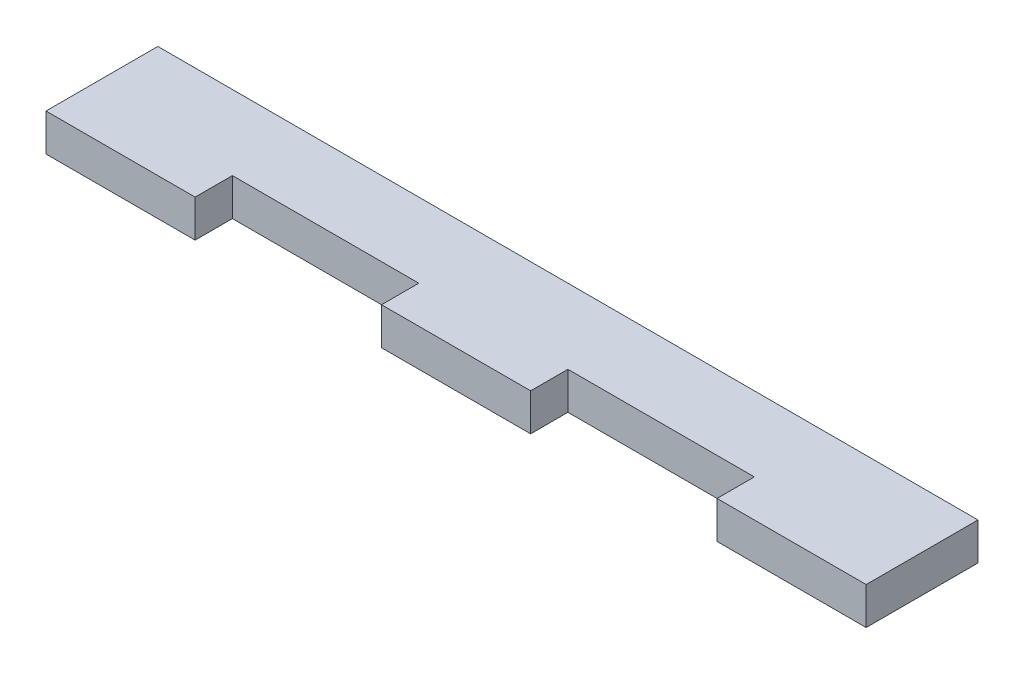
SolidWorks part; units mm, degrees
ref_plane "Front Plane" through (0, 0, 0) normal (0, 0, 1) x (1, 0, 0)
ref_plane "Top Plane" through (0, 0, 0) normal (0, 1, 0) x (1, 0, 0)
ref_plane "Right Plane" through (0, 0, 0) normal (1, 0, 0) x (0, 0, -1)
sketch "Sketch1" plane through (0, 0, 0) normal (0, 1, 0) x (1, 0, 0)
  line L0 (-12.7, -6.35) -> (-12.7, -12.7)
  line L1 (-44.45, -6.35) -> (-12.7, -6.35)
  line L2 (-69.85, -6.35) -> (-69.85, 6.35)
  line L3 (-69.85, 6.35) -> (69.85, 6.35)
  line L4 (69.85, -6.35) -> (69.85, 6.35)
  line L5 (-69.85, -6.35) -> (69.85, 6.35) construction
  line L6 (-69.85, 6.35) -> (69.85, -6.35) construction
  line L7 (12.7, -6.35) -> (44.45, -6.35)
  line L8 (-69.85, -6.35) -> (-69.85, -12.7)
  line L9 (-69.85, -12.7) -> (-44.45, -12.7)
  line L10 (-44.45, -6.35) -> (-44.45, -12.7)
  line L11 (-12.7, -12.7) -> (12.7, -12.7)
  line L12 (12.7, -6.35) -> (12.7, -12.7)
  line L13 (44.45, -6.35) -> (44.45, -12.7)
  line L14 (44.45, -12.7) -> (69.85, -12.7)
  line L15 (69.85, -6.35) -> (69.85, -12.7)
  point P0 (0, 0)
  dimension "D1" = 139.7
  dimension "D2" = 12.7
  dimension "D3" = 6.35
  dimension "D4" = 25.4
  dimension "D5" = 3
extrude "Boss-Extrude1" add sketch "Sketch1" along normal blind 6.35
